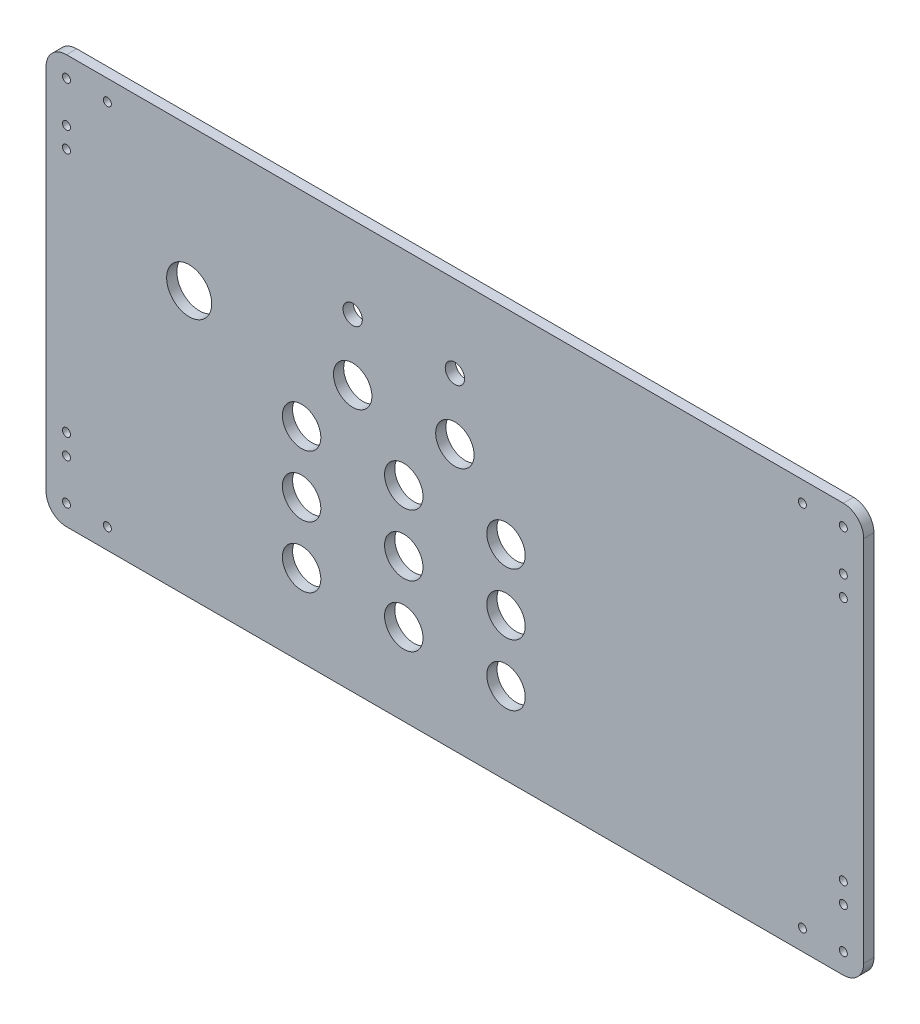
SolidWorks part; units mm, degrees
material "PC High Viscosity"
ref_plane "Front Plane" through (0, 0, 0) normal (0, 0, 1) x (1, 0, 0)
ref_plane "Top Plane" through (0, 0, 0) normal (0, 1, 0) x (1, 0, 0)
ref_plane "Right Plane" through (0, 0, 0) normal (1, 0, 0) x (0, 0, -1)
sketch "Sketch1" plane through (0, 0, 0) normal (0, 0, 1) x (1, 0, 0)
  line L1 (0, 0) -> (508, 0)
  line L2 (0, 0) -> (0, 254)
  line L3 (0, 254) -> (508, 254)
  line L4 (508, 0) -> (508, 254)
  dimension "D1" = 508
  dimension "D2" = 254
extrude "Boss-Extrude1" add sketch "Sketch1" along normal blind 6.35
sketch "Sketch3" plane through (0, 0, 0) normal (0, 0, -1) x (-1, 0, 0)
  line L0 (0, 0) -> (-508, 0) construction
  line L11 (-508, 254) -> (0, 254) construction
  line L17 (0, 254) -> (0, 0) construction
  line L18 (-508, 0) -> (-508, 254) construction
  line L19 (0, 254) -> (-25.4, 254) construction
  line L20 (0, 254) -> (0, 0) construction
  line L21 (0, 0) -> (-25.4, 0) construction
  line L22 (-25.4, 254) -> (-25.4, 0) construction
  line L23 (-508, 0) -> (-25.4, 0) construction
  line L24 (-508, 0) -> (-508, 25.4) construction
  line L25 (-508, 25.4) -> (-25.4, 25.4) construction
  line L26 (-25.4, 0) -> (-25.4, 25.4) construction
  line L27 (-508, 254) -> (-25.4, 254) construction
  line L28 (-508, 254) -> (-508, 228.6) construction
  line L29 (-508, 228.6) -> (-25.4, 228.6) construction
  line L30 (-25.4, 254) -> (-25.4, 228.6) construction
  circle A8 centre (-158.75, 88.9) radius 11.938
  circle A10 centre (-222.25, 88.9) radius 11.938
  circle A11 centre (-158.75, 50.8) radius 11.938
  circle A13 centre (-222.25, 50.8) radius 11.938
  circle A15 centre (-222.25, 127) radius 11.938
  circle A16 centre (-285.75, 127) radius 11.938
  circle A17 centre (-285.75, 88.9) radius 11.938
  circle A18 centre (-285.75, 50.8) radius 11.938
  circle A19 centre (-254, 203.2) radius 6
  circle A20 centre (-190.5, 203.2) radius 6
  circle A21 centre (-158.75, 127) radius 11.938
  circle A23 centre (-190.5, 165.1) radius 11.938
  circle A24 centre (-254, 165.1) radius 11.938
  circle A27 centre (-88.9, 165.1) radius 14
  circle A28 centre (-88.9, 165.1) radius 49.25 construction
  dimension "D2" = 12
  dimension "D3" = 63.5
  dimension "D4" = 38.1
  dimension "D5" = 38.1
  dimension "D6" = 63.5
  dimension "D7" = 25.4
  dimension "D8" = 38.1
  dimension "D9" = 38.1
  dimension "D10" = 25.4
  dimension "D11" = 23.876
  dimension "D12" = 63.5
  dimension "D13" = 28
  dimension "D14" = 98.5
  dimension "D15" = 31.75
  dimension "D21" = 12
  dimension "D22" = 23.876
  dimension "D16" = 50.8
  dimension "D17" = 25.4
  dimension "D18" = 88.9
  dimension "D19" = 88.9
  dimension "D20" = 254
extrude "Cut-Extrude2" cut sketch "Sketch3" against normal through all contours A18 | A17 | A16 | A24 | A10 | A8 | A23 | A11 | A13 | A15 | A21 | A27 | A20 | A19 region at (158.75, 88.9, 0) region at (222.25, 88.9, 0) region at (158.75, 50.8, 0) region at (222.25, 50.8, 0) region at (285.75, 127, 0) region at (285.75, 88.9, 0) region at (285.75, 50.8, 0) region at (190.5, 165.1, 0) region at (254, 165.1, 0)
fillet "Fillet1" radius 12.7 4 edges at (508, 0, 3.175) (0, 0, 3.175) (0, 254, 3.175) (508, 254, 3.175)
sketch "Sketch4" plane through (0, 0, 0) normal (0, 0, -1) x (-1, 0, 0)
  line L8 (-508, 12.7) -> (-508, 241.3) construction
  line L9 (-254, 0) -> (-254, 254) construction
  line L10 (-12.7, 0) -> (-495.3, 0) construction
  line L11 (-495.3, 254) -> (-12.7, 254) construction
  line L12 (-618.7392, 127) -> (68.6032, 127) construction
  circle A2 centre (-495.3205, 241.3) radius 2.4892
  circle A3 centre (-469.9205, 241.3) radius 2.4892
  circle A6 centre (-495.3205, 215.9) radius 2.4892
  circle A7 centre (-495.3205, 203.2) radius 2.4892
  circle A16 centre (-469.9205, 12.7) radius 2.4892
  circle A17 centre (-495.3205, 50.8) radius 2.4892
  circle A18 centre (-495.3205, 38.1) radius 2.4892
  circle A19 centre (-495.3205, 12.7) radius 2.4892
  circle A20 centre (-12.6795, 50.8) radius 2.4892
  circle A21 centre (-12.6795, 38.1) radius 2.4892
  circle A22 centre (-12.6795, 12.7) radius 2.4892
  circle A23 centre (-38.0795, 12.7) radius 2.4892
  circle A24 centre (-12.6795, 203.2) radius 2.4892
  circle A25 centre (-12.6795, 215.9) radius 2.4892
  circle A26 centre (-12.6795, 241.3) radius 2.4892
  circle A27 centre (-38.0795, 241.3) radius 2.4892
  dimension "D2" = 12.6795
  dimension "D8" = 127
  dimension "D5" = 4.9784
  dimension "D6" = 4.9784
  dimension "D7" = 12.7
  dimension "D3" = 38.1
  dimension "D4" = 50.8
  dimension "D13" = 25.4
extrude "Cut-Extrude3" cut sketch "Sketch4" against normal through all
sketch "Sketch5" plane through (0, 0, 6.35) normal (0, 0, -1) x (-1, 0, 0)
  line L0 (0, -912.4813) -> (0, 49087.5187) construction
  line L1 (-989.5448, 0) -> (49010.4552, 0) construction
  point P3 (0, 0)
  point P5 (0, 0)
